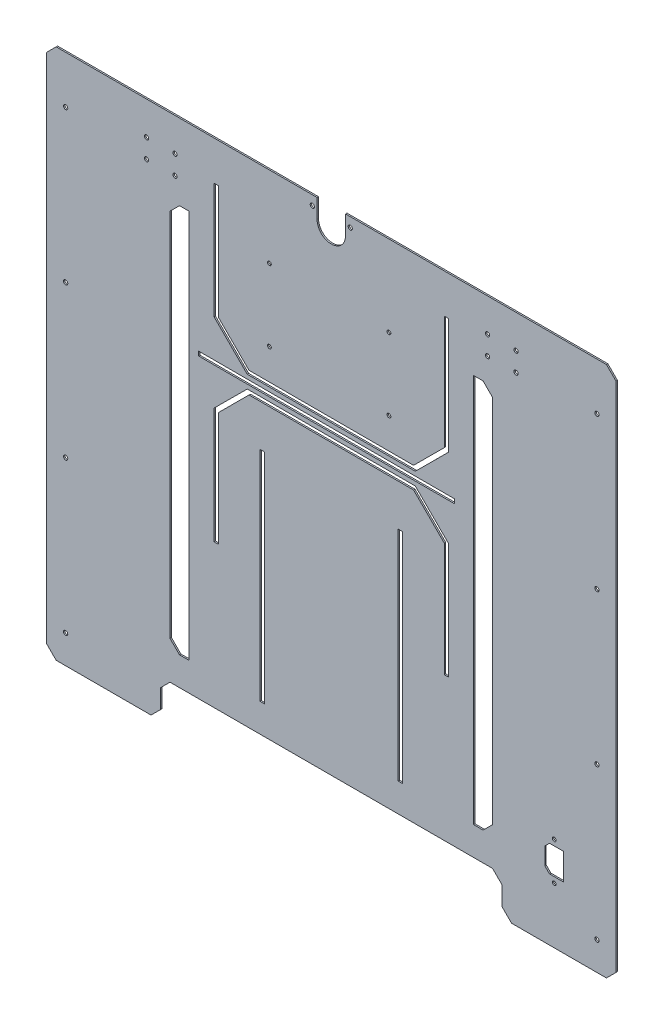
SolidWorks part; units mm, degrees
ref_plane "Front Plane" through (0, 0, 0) normal (0, 0, 1) x (1, 0, 0)
ref_plane "Top Plane" through (0, 0, 0) normal (0, 1, 0) x (1, 0, 0)
ref_plane "Right Plane" through (0, 0, 0) normal (1, 0, 0) x (0, 0, -1)
sketch "Sketch1" plane through (0, 0, 0) normal (0, 0, 1) x (1, 0, 0)
  line L0 (440.3197, -451.5188) -> (440.3197, -431.5188)
  line L1 (430.3197, -421.5188) -> (310.3197, -421.5188)
  line L2 (560.3197, -5.0048) -> (560.3197, 98.4812)
  line L3 (80.3197, -431.5188) -> (80.3197, -451.5188)
  line L4 (560.3197, 98.4812) -> (540.3197, 98.4812)
  line L5 (531.5264, 93.7193) -> (531.5264, -420.0048) construction
  line L6 (560.3197, -5.0048) -> (560.3197, -420.0048)
  line L7 (0.3197, 98.4812) -> (540.3197, 98.4812)
  line L8 (2.3197, -461.5188) -> (70.3197, -461.5188)
  line L9 (450.3197, -461.5188) -> (540.3197, -461.5188)
  line L10 (440.3197, -431.5188) -> (430.3197, -421.5188)
  line L11 (503.536, -23.973) -> (503.536, -80.4204) construction
  line L12 (-39.6803, -421.5188) -> (-39.6803, -5.0048)
  line L14 (450.3197, -461.5188) -> (440.3197, -451.5188)
  line L18 (0.3197, 98.4812) -> (-39.6803, 98.4812)
  line L19 (-39.6803, 98.4812) -> (-39.6803, -5.0048)
  line L20 (-39.6803, -421.5188) -> (-39.6803, -451.5188)
  line L21 (-29.6803, -461.5188) -> (2.3197, -461.5188)
  line L22 (560.3197, -420.0048) -> (560.3197, -451.5188)
  line L23 (550.3197, -461.5188) -> (540.3197, -461.5188)
  line L24 (90.3197, -421.5188) -> (80.3197, -431.5188)
  line L25 (80.3197, -451.5188) -> (70.3197, -461.5188)
  line L26 (560.3197, -451.5188) -> (550.3197, -461.5188)
  line L27 (-39.6803, -451.5188) -> (-29.6803, -461.5188)
  line L31 (210.3197, -421.5188) -> (90.3197, -421.5188)
  line L34 (310.3197, -421.5188) -> (210.3197, -421.5188)
  point P0 (440.3197, -461.5188)
  point P5 (440.3197, -421.5188)
  point P27 (-39.6803, -461.5188)
  point P28 (560.3197, -461.5188)
  point P29 (80.3197, -421.5188)
  point P30 (80.3197, -461.5188)
  point P42 (300.3197, -421.5188)
  point P46 (220.3197, -421.5188)
  dimension "D1" = 560
  dimension "D2" = 10
  dimension "D3" = 600
  dimension "D4" = 120
  dimension "D9" = 120
  dimension "D19" = 40
  dimension "D21" = 10
  dimension "D22" = 10
extrude "Boss-Extrude1" add sketch "Sketch1" along normal blind 1.5
sketch "Sketch3" plane through (0, 0, 0) normal (0, 0, -1) x (-1, 0, 0)
  line L1 (-410.3197, -391.5188) -> (-420.3197, -391.5188)
  line L2 (-410.3197, -391.5188) -> (-410.3197, 18.4812)
  line L3 (-410.3197, 18.4812) -> (-420.3197, 18.4812)
  line L4 (-430.3197, -381.5188) -> (-430.3197, 8.4812)
  line L5 (-420.3197, -391.5188) -> (-430.3197, -381.5188)
  line L6 (-420.3197, 18.4812) -> (-430.3197, 8.4812)
  line L7 (-560.3197, 98.4812) -> (39.6803, 98.4812) construction
  line L8 (-90.3197, -421.5188) -> (-430.3197, -421.5188) construction
  line L9 (-260.3197, -421.5188) -> (-260.3197, -274.4779) construction
  line L10 (-100.3197, 18.4812) -> (-90.3197, 8.4812)
  line L11 (-100.3197, -391.5188) -> (-90.3197, -381.5188)
  line L12 (-90.3197, -381.5188) -> (-90.3197, 8.4812)
  line L13 (-110.3197, 18.4812) -> (-100.3197, 18.4812)
  line L14 (-110.3197, -391.5188) -> (-110.3197, 18.4812)
  line L15 (-110.3197, -391.5188) -> (-100.3197, -391.5188)
  line L17 (-560.3197, -451.5188) -> (-560.3197, 98.4812) construction
  point P1 (-430.3197, 18.4812)
  point P3 (-430.3197, -391.5188)
  point P22 (-90.3197, -391.5188)
  point P23 (-90.3197, 18.4812)
  dimension "D1" = 20
  dimension "D2" = 80
  dimension "D3" = 30
  dimension "D5" = 130
extrude "Cut-Extrude2" cut sketch "Sketch3" against normal blind 10
sketch "Sketch4" plane through (0, 0, 0) normal (0, 0, -1) x (-1, 0, 0)
  line L6 (-390.3197, -104.1791) -> (-120.3197, -104.1791)
  line L8 (-390.3197, -108.6791) -> (-120.3197, -108.6791)
  line L11 (-260.3197, -104.1791) -> (-260.3197, -60.3431) construction
  line L13 (-100.3197, -106.4291) -> (-92.2726, -106.4291) construction
  line L16 (-390.3197, -104.1791) -> (-390.3197, -108.6791)
  line L20 (-410.3197, -391.5188) -> (-410.3197, 18.4812) construction
  line L35 (-120.3197, -104.1791) -> (-120.3197, -108.6791)
  dimension "D1" = 20
extrude "Cut-Extrude5" cut sketch "Sketch4" against normal blind 10
sketch "Sketch5" plane through (0, 0, 0) normal (0, 0, -1) x (-1, 0, 0)
  line L0 (-171.7435, -99.6791) -> (-260.3197, -99.6791)
  line L1 (-260.3197, -99.6791) -> (-260.3197, -95.1791)
  line L2 (-260.3197, -95.1791) -> (-173.604, -95.1791)
  line L3 (-173.604, -95.1791) -> (-141.2435, -62.9017)
  line L4 (-141.2435, -62.9017) -> (-141.2435, 57.2547)
  line L5 (-141.2435, 57.2547) -> (-136.7435, 57.2547)
  line L6 (-136.7435, 57.2547) -> (-136.7435, -64.7691)
  line L7 (-136.7435, -64.7691) -> (-171.7435, -99.6791)
  line L8 (-120.3197, -104.1791) -> (-390.3197, -104.1791) construction
  dimension "D1" = 4.5
  dimension "D2" = 4.5
  dimension "D3" = 4.5
  dimension "D5" = 35
  dimension "D6" = 4.5
extrude "Cut-Extrude6" cut sketch "Sketch5" against normal blind 10
mirror "Mirror3" about plane through (260.3197, -99.6791, 10) normal (1, 0, 0) of "Cut-Extrude6"
ref_plane "Plane1" through (0, -106.4291, 0) normal (0, -1, 0) x (-1, 0, 0)
mirror "Mirror9" about plane through (0, -106.4291, 0) normal (0, -1, 0) of face at (141.2435, -2.8235, 0.75) of face at (136.7435, -3.7572, 0.75) of face at (379.396, -2.8235, 0.75) of face at (383.896, -3.7572, 0.75) of face at (366.396, -82.2241, 0.75) of face at (381.646, 57.2547, 0.75) of face at (363.2157, -79.0404, 0.75) of face at (260.3197, -95.1791, 0.75) of face at (157.4238, -79.0404, 0.75) of face at (138.9935, 57.2547, 0.75) of face at (154.2435, -82.2241, 0.75) of face at (260.3197, -99.6791, 0.75)
chamfer "Chamfer1" distance 10 angle 45 2 edges at (-39.6803, 98.4812, 0.75) (560.3197, 98.4812, 0.75)
sketch "Sketch6" plane through (0, 0, 0) normal (0, 0, -1) x (-1, 0, 0)
  line L0 (-560.3197, -451.5188) -> (-560.3197, 88.4812) construction
  line L1 (-550.3197, 98.4812) -> (29.6803, 98.4812) construction
  circle A0 centre (-540.3197, 48.4812) radius 2.25
  circle A1 centre (-540.3197, -111.5188) radius 2.25
  circle A2 centre (-540.3197, -271.5188) radius 2.25
  circle A3 centre (-540.3197, -431.5188) radius 2.25
  dimension "D2" = 4.5
  dimension "D1" = 20
  dimension "D3" = 50
  dimension "D4" = 4
extrude "Cut-Extrude7" cut sketch "Sketch6" against normal blind 10
ref_plane "Plane2" through (260.3197, 0, 0) normal (1, 0, 0) x (0, 0, -1)
mirror "Mirror10" about plane through (260.3197, 0, 0) normal (1, 0, 0) of "Cut-Extrude7"
sketch "Sketch7" plane through (0, 0, 1.5) normal (0, 0, 1) x (1, 0, 0)
  line L0 (65.6049, 63.4812) -> (95.6049, 63.4812) construction
  line L1 (95.6049, 63.4812) -> (95.6049, 43.4812) construction
  line L2 (95.6049, 43.4812) -> (65.6049, 43.4812) construction
  line L3 (65.6049, 63.4812) -> (65.6049, 98.4812) construction
  line L4 (550.3197, 98.4812) -> (-29.6803, 98.4812) construction
  circle A0 centre (65.6049, 63.4812) radius 2.25
  circle A2 centre (95.6049, 63.4812) radius 2.25
  circle A3 centre (95.6049, 43.4812) radius 2.25
  circle A4 centre (65.6049, 43.4812) radius 2.25
  dimension "D1" = 4.5
  dimension "D2" = 30
  dimension "D3" = 20
  dimension "D4" = 30
  dimension "D5" = 35
extrude "Cut-Extrude8" cut sketch "Sketch7" against normal blind 10
mirror "Mirror11" about plane through (260.3197, 0, 0) normal (1, 0, 0) of "Cut-Extrude8"
sketch "Sketch8" plane through (0, 0, 0) normal (0, 0, -1) x (-1, 0, 0)
  line L0 (-260.3197, 98.4812) -> (-260.3197, 78.4812) construction
  line L1 (-550.3197, 98.4812) -> (29.6803, 98.4812) construction
  line L2 (-275.3197, 78.4812) -> (-275.3197, 98.4812)
  line L3 (-275.3197, 98.4812) -> (-245.3197, 98.4812)
  line L4 (-245.3197, 98.4812) -> (-245.3197, 78.4812)
  line L5 (-280.3197, 88.4812) -> (-275.3197, 88.4812) construction
  line L6 (-275.3197, 88.4812) -> (-240.3197, 88.4812) construction
  arc A0 (-275.3197, 78.4812) -> (-245.3197, 78.4812) centre (-260.3197, 78.4812) ccw
  circle A1 centre (-280.3197, 88.4812) radius 2.25
  circle A2 centre (-240.3197, 88.4812) radius 2.25
  point P12 (-245.3197, 88.4812)
  dimension "D1" = 30
  dimension "D5" = 4.5
  dimension "D6" = 4.5
  dimension "D2" = 20
  dimension "D3" = 5
  dimension "D4" = 5
extrude "Cut-Extrude9" cut sketch "Sketch8" against normal blind 10
sketch "Sketch9" plane through (0, 0, 0) normal (0, 0, -1) x (-1, 0, 0)
  circle A0 centre (-321.0913, -62.7791) radius 2
  circle A1 centre (-195.0913, -62.7791) radius 2
  circle A2 centre (-195.0913, 13.2209) radius 2
  circle A3 centre (-321.0913, 13.2209) radius 2
  circle A4 centre (-321.0913, 13.2209) radius 2 construction
  circle A5 centre (-195.0913, 13.2209) radius 2 construction
  circle A6 centre (-195.0913, -62.7791) radius 2 construction
  circle A7 centre (-321.0913, -62.7791) radius 2 construction
  dimension "D1" = 4
extrude "Cut-Extrude10" cut sketch "Sketch9" against normal blind 27
sketch "Sketch10" plane through (0, 0, 0) normal (0, 0, -1) x (-1, 0, 0)
  line L0 (-420.3197, -391.5188) -> (-410.3197, -391.5188) construction
  line L1 (-335.3197, -161.5188) -> (-330.8197, -161.5188)
  line L2 (-335.3197, -161.5188) -> (-335.3197, -391.5188)
  line L3 (-335.3197, -391.5188) -> (-330.8197, -391.5188)
  line L4 (-330.8197, -161.5188) -> (-330.8197, -391.5188)
  line L5 (-189.8197, -391.5188) -> (-185.3197, -391.5188)
  line L6 (-189.8197, -391.5188) -> (-189.8197, -161.5188)
  line L7 (-189.8197, -161.5188) -> (-185.3197, -161.5188)
  line L8 (-185.3197, -391.5188) -> (-185.3197, -161.5188)
  line L9 (-410.3197, -391.5188) -> (-410.3197, 18.4812) construction
  dimension "D1" = 4.5
  dimension "D2" = 4.5
  dimension "D3" = 230
  dimension "D4" = 75
  dimension "D5" = 75
extrude "Cut-Extrude11" cut sketch "Sketch10" against normal blind 10
sketch "Sketch11" plane through (0, 0, 1.5) normal (0, 0, 1) x (1, 0, 0)
  line L0 (490.3197, -368.5188) -> (485.3197, -373.5188)
  line L1 (505.3197, -368.5188) -> (490.3197, -368.5188)
  line L2 (505.3197, -368.5188) -> (505.3197, -396.5188)
  line L3 (505.3197, -396.5188) -> (490.3197, -396.5188)
  line L4 (485.3197, -373.5188) -> (485.3197, -391.5188)
  line L5 (490.3197, -396.5188) -> (485.3197, -391.5188)
  line L6 (560.3197, -451.5188) -> (560.3197, 88.4812) construction
  line L7 (450.3197, -461.5188) -> (550.3197, -461.5188) construction
  circle A0 centre (495.3197, -362.5188) radius 2
  circle A1 centre (495.3197, -402.5188) radius 2
  point P1 (485.3197, -396.5188)
  point P3 (485.3197, -368.5188)
  point P14 (505.3197, -382.5188)
  dimension "D8" = 4
  dimension "D1" = 20
  dimension "D2" = 28
  dimension "D3" = 55
  dimension "D4" = 10
  dimension "D5" = 10
  dimension "D6" = 40
  dimension "D7" = 20
  dimension "D9" = 65
extrude "Cut-Extrude12" cut sketch "Sketch11" against normal blind 10
